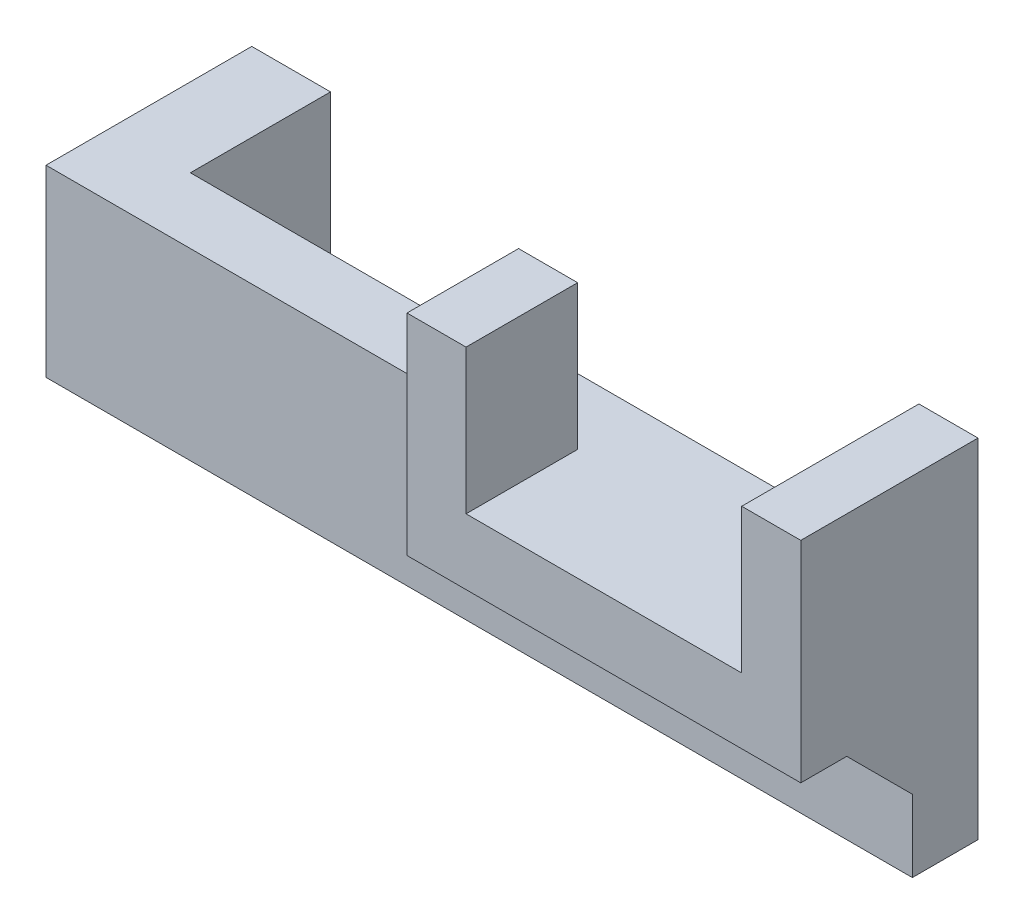
SolidWorks part; units mm, degrees
ref_plane "Front Plane" through (0, 0, 0) normal (0, 0, 1) x (1, 0, 0)
ref_plane "Top Plane" through (0, 0, 0) normal (0, 1, 0) x (1, 0, 0)
ref_plane "Right Plane" through (0, 0, 0) normal (1, 0, 0) x (0, 0, -1)
sketch "Sketch1" plane through (0, 0, 0) normal (1, 0, 0) x (0, 0, -1)
  line L1 (0, 0) -> (31.35, 0)
  line L2 (0, 0) -> (0, 28)
  line L3 (0, 28) -> (31.35, 28)
  line L4 (31.35, 0) -> (31.35, 28)
  dimension "D1" = 28
  dimension "D2" = 31.35
extrude "Boss-Extrude1" add sketch "Sketch1" along normal blind 12
sketch "Sketch2" plane through (12, 0, 0) normal (1, 0, 0) x (0, 0, -1)
  line L0 (31.35, 28) -> (0, 28) construction
  line L1 (0, 0) -> (10, 0)
  line L2 (0, 0) -> (0, 28)
  line L3 (0, 28) -> (10, 28)
  line L4 (10, 0) -> (10, 28)
  dimension "D1" = 10
extrude "Boss-Extrude2" add sketch "Sketch2" along normal blind 120
sketch "Sketch3" plane through (0, 0, 0) normal (0, 0, 1) x (1, 0, 0)
  line L1 (132, 28) -> (72, 28)
  line L2 (132, 28) -> (132, 53)
  line L3 (132, 53) -> (72, 53)
  line L4 (72, 28) -> (72, 53)
  dimension "D1" = 25
  dimension "D2" = 60
extrude "Boss-Extrude3" add sketch "Sketch3" against normal blind 10
sketch "Sketch4" plane through (0, 0, 0) normal (0, 0, 1) x (1, 0, 0)
  line L0 (81, 53) -> (81, 31)
  line L1 (132, 53) -> (72, 53) construction
  line L2 (81, 31) -> (123, 31)
  line L3 (123, 31) -> (123, 53)
  line L4 (72, 53) -> (72, 28) construction
  line L5 (81, 53) -> (123, 53)
  dimension "D1" = 42
  dimension "D2" = 9
  dimension "D3" = 22
extrude "Cut-Extrude1" cut sketch "Sketch4" against normal through all
sketch "Sketch5" plane through (0, 0, 0) normal (0, 0, 1) x (1, 0, 0)
  line L0 (81, 53) -> (72, 53)
  line L1 (72, 53) -> (72, 0)
  line L2 (132, 0) -> (0, 0) construction
  line L3 (72, 0) -> (132, 0)
  line L4 (132, 0) -> (132, 53)
  line L5 (132, 53) -> (123, 53)
  line L6 (123, 53) -> (123, 31)
  line L7 (123, 31) -> (81, 31)
  line L8 (81, 31) -> (81, 53)
  line L9 (72, 21) -> (132, 21)
  line M1 (132, 53) -> (123, 53)
  line M2 (123, 53) -> (123, 31)
  line M3 (123, 31) -> (81, 31)
  line M4 (81, 31) -> (81, 53)
  line M5 (81, 53) -> (72, 53)
  line M6 (72, 53) -> (72, 28)
  dimension "D1" = 10
extrude "Boss-Extrude4" add sketch "Sketch5" along normal blind 17 contours L1 L9 L4 M1 M2 M3 M4 M5 M6 region at (80.32, 42, 0)
chamfer "Chamfer1" distance 10 angle 45 2 edges at (72, 24.5, 0) (102, 21, 0)
fillet "Fillet1" [suppressed] radius 10
sketch "Sketch6" plane through (72, 0, 0) normal (-1, 0, 0) x (0, 0, 1)
  line L0 (0, 53) -> (0, 28)
  line L1 (-10, 53) -> (17, 53) construction
  line L2 (-10, 28) -> (10, 28) construction
  line L3 (-10, 53) -> (-10, 28) construction
  line L4 (0, 28) -> (-10, 28)
  line L5 (-10, 28) -> (-10, 53)
  line L6 (-10, 53) -> (0, 53)
  line L7 (0, 31) -> (-10, 31)
  line M9 (17, 53) -> (-10, 53)
  line M10 (-10, 53) -> (-10, 28)
  dimension "D1" = 10
  dimension "D2" = 22
extrude "Cut-Extrude2" cut sketch "Sketch6" against normal blind 9 contours L7 L0 M9 M10 region at (72, 42, -5)
chamfer "Chamfer2" distance 10 angle 45 1 edges at (72, 28, 0)
